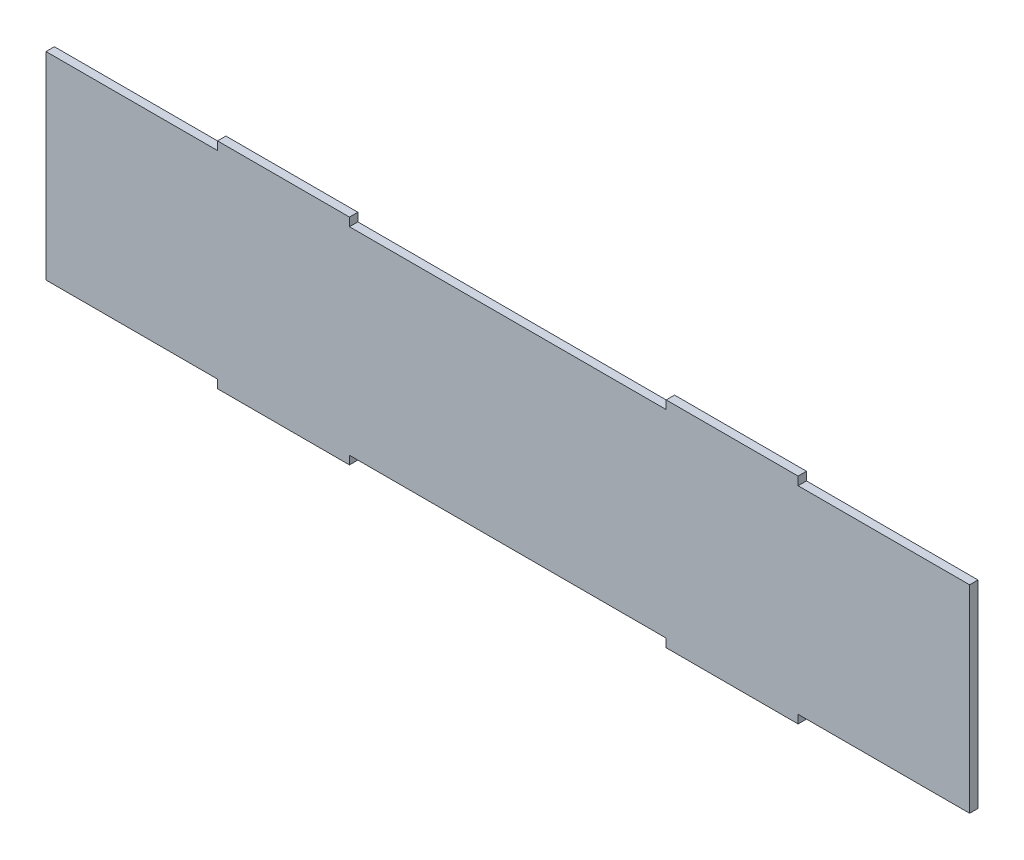
SolidWorks part; units mm, degrees
ref_plane "Front Plane" through (0, 0, 0) normal (0, 0, 1) x (1, 0, 0)
ref_plane "Top Plane" through (0, 0, 0) normal (0, 1, 0) x (1, 0, 0)
ref_plane "Right Plane" through (0, 0, 0) normal (1, 0, 0) x (0, 0, -1)
sketch "Sketch2" plane through (0, 0, 0) normal (0, 0, 1) x (1, 0, 0)
  line L0 (0, 0) -> (65, 0)
  line L1 (0, 0) -> (350, 0) construction
  line L2 (0, 0) -> (0, 75) construction
  line L3 (0, 75) -> (350, 75) construction
  line L4 (350, 0) -> (350, 75) construction
  line L5 (65, 0) -> (65, -3.175)
  line L6 (65, -3.175) -> (115, -3.175)
  line L7 (115, -3.175) -> (115, 0)
  line L8 (115, 0) -> (235, 0)
  line L9 (235, 0) -> (235, -3.175)
  line L10 (235, -3.175) -> (285, -3.175)
  line L11 (285, -3.175) -> (285, 0)
  line L12 (285, 0) -> (350, 0)
  line L13 (350, 0) -> (350, 75)
  line L14 (350, 75) -> (285, 75)
  line L15 (285, 75) -> (285, 78.175)
  line L16 (285, 78.175) -> (235, 78.175)
  line L17 (235, 78.175) -> (235, 75)
  line L18 (235, 75) -> (115, 75)
  line L19 (115, 75) -> (115, 78.175)
  line L20 (115, 78.175) -> (65, 78.175)
  line L21 (65, 78.175) -> (65, 75)
  line L22 (65, 75) -> (0, 75)
  line L23 (0, 75) -> (0, 0)
  dimension "D1" = 3.175
  dimension "D2" = 75
  dimension "D3" = 350
  dimension "D4" = 50
  dimension "D5" = 65
extrude "Boss-Extrude1" add sketch "Sketch2" along normal blind 3.175
